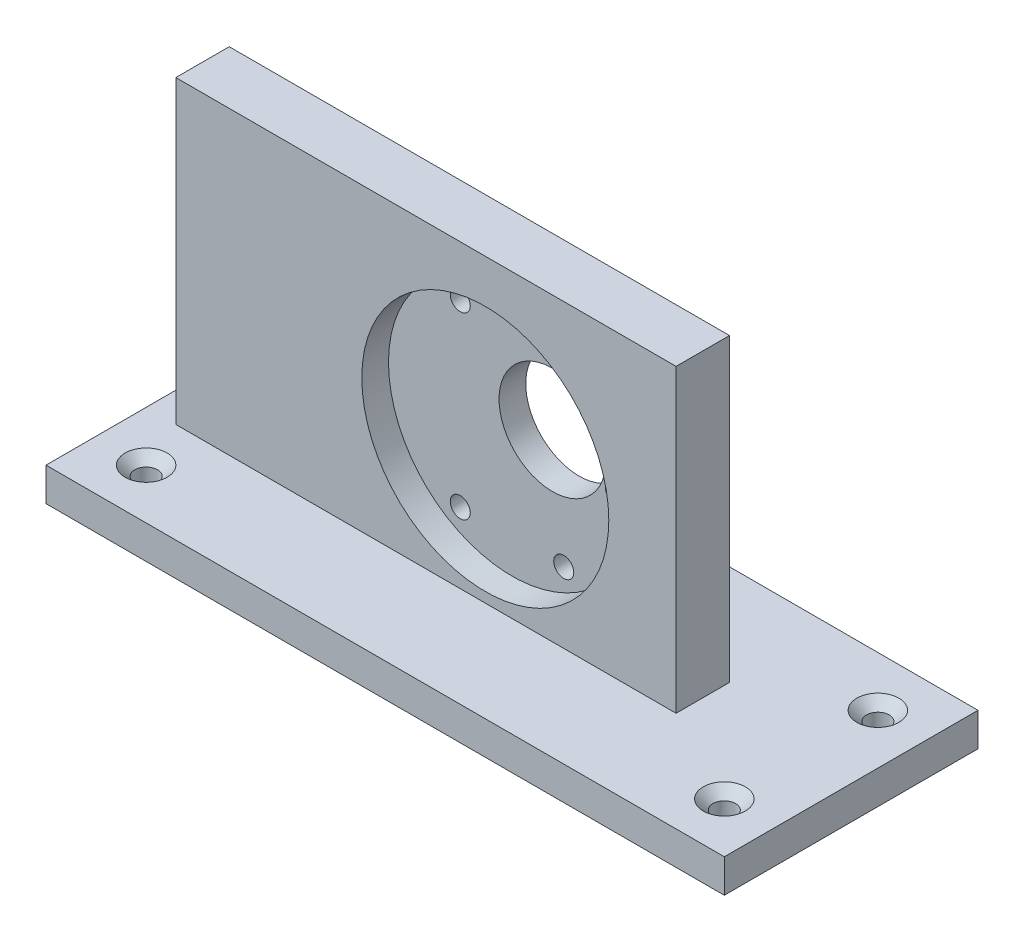
SolidWorks part; units mm, degrees
note: The reader was unsure of these and kept them because the rebuilt part matched: shared geometry of "Sketch3<3>".
other "Markup1"
sketch "Sketch5" plane through (25, 50, 8) normal (0.9645, 0.1424, 0.2224) x (0.1697, 0.3107, -0.9352)
ref_plane "Front Plane" through (0, 0, 0) normal (0, 0, 1) x (1, 0, 0)
ref_plane "Top Plane" through (0, 0, 0) normal (0, 1, 0) x (1, 0, 0)
ref_plane "Right Plane" through (0, 0, 0) normal (1, 0, 0) x (0, 0, -1)
sketch "Sketch3" plane through (0, 0, 0) normal (0, 0, 1) x (1, 0, 0)
  line L1 (-28.575, 50) -> (28.575, 50)
  line L2 (-28.575, 50) -> (-28.575, 0)
  line L3 (-28.575, 0) -> (28.575, 0)
  line L4 (28.575, 50) -> (28.575, 0)
  line L5 (-7.75, 38.4234) -> (7.75, 38.4234) construction
  line L6 (7.75, 38.4234) -> (15.5, 25) construction
  line L7 (15.5, 25) -> (7.75, 11.5766) construction
  line L8 (7.75, 11.5766) -> (-7.75, 11.5766) construction
  line L9 (-7.75, 11.5766) -> (-15.5, 25) construction
  line L10 (-15.5, 25) -> (-7.75, 38.4234) construction
  line L12 (-20.1843, 13.3466) -> (22.8058, 38.167) construction
  circle A5 centre (-7.75, 38.4234) radius 1.5
  circle A6 centre (7.75, 38.4234) radius 1.5
  circle A8 centre (-7.75, 11.5766) radius 1.5
  circle A9 centre (7.75, 11.5766) radius 1.5
  circle A10 centre (15.5, 25) radius 1.5
  circle A11 centre (6.0622, 28.5) radius 8
  point P4 (0, 0)
  point P27 (-11.625, 18.2883)
  point P28 (11.625, 31.7117)
  dimension "D4" = 25
  dimension "D9" = 16
  dimension "D3" = 3
  dimension "D1" = 50
  dimension "D2" = 57.15
  dimension "D6" = 120
  dimension "D7" = 120
  dimension "D8" = 15.5
  dimension "D10" = 6.4234
extrude "Boss-Extrude1" add sketch "Sketch3" along normal blind 8 contours L2 L3 L4 L1
extrude "Cut-Extrude2" cut sketch "Sketch3<3>" along normal blind 10
sketch "Sketch3<3>" plane through (0, 0, 0) normal (0, 0, 1) x (1, 0, 0) same geometry as "Sketch3"
sketch "Sketch4" plane through (0, 0, 8) normal (0, 0, 1) x (1, 0, 0)
  line L0 (-15.5, 25) -> (15.5, 25) construction
  circle A0 centre (0, 25) radius 18.5
  dimension "D1" = 37
extrude "Cut-Extrude3" cut sketch "Sketch4" against normal blind 4 contours A0
sketch "Sketch6" plane through (0, 0, 8) normal (0, 0, 1) x (1, 0, 0)
  line L1 (-50.8, 5) -> (50.8, 5)
  line L2 (-50.8, 5) -> (-50.8, 0)
  line L3 (-50.8, 0) -> (50.8, 0)
  line L4 (50.8, 5) -> (50.8, 0)
  point P4 (0, 0)
  dimension "D1" = 101.6
  dimension "D2" = 5
extrude "Boss-Extrude2" add sketch "Sketch6" against normal blind 23 and the other way blind 15
sketch "Sketch7" plane through (0, 5, 0) normal (0, 1, 0) x (1, 0, 0)
  line L0 (-50.8, -23) -> (-50.8, 15) construction
  line L1 (-50.8, -23) -> (-43.3, -23)
  line L2 (-50.8, -23) -> (-50.8, -15.5)
  line L3 (-50.8, -15.5) -> (-43.3, -15.5)
  line L4 (-43.3, -23) -> (-43.3, -15.5)
  line L5 (-50.8, -4) -> (50.8, -4) construction
  line L6 (50.8, -23) -> (50.8, 15) construction
  line L7 (0, 15) -> (0, -23) construction
  line L8 (50.8, 15) -> (-50.8, 15) construction
  line L9 (50.8, -23) -> (-50.8, -23) construction
  point P18 (-43.3, 7.5)
  point P20 (43.3, -15.5)
  point P21 (43.3, 7.5)
  dimension "D1" = 7.5
hole_wizard "CSK for M3 Flat Head Machine Screw1" positions "Sketch8" profile "Sketch9" countersink size "M3" standard "ANSI Metric" end condition through all
sketch "Sketch8" plane through (0, 5, 0) normal (0, 1, 0) x (1, 0, 0)
  point P0 (-43.3, 7.5)
  point P3 (-43.3, -15.5)
  point P6 (43.3, -15.5)
  point P9 (43.3, 7.5)
sketch "Sketch9" plane through (-43.3, 5, -7.5) normal (1, 0, 0) x (0, 0, 1)
  line L0 (0, 0) -> (0, 5)
  line L1 (0, 5) -> (1.7, 5)
  line L2 (1.7, 5) -> (1.7, 1.45)
  line L3 (1.7, 1.45) -> (3.15, 0)
  line L5 (3.15, 0) -> (0, 0)
  line L6 (-1.7, 1.45) -> (-3.15, 0) construction
  line L11 (0, -6.35) -> (0, 107.95) construction
  dimension "Thru Hole Dia." = 3.4
  dimension "Thru Hole Depth" = 5
  dimension "Near C'Sink Dia." = 6.3
  dimension "Near C'Sink Angle" = 90
extrude "Cut-Extrude6" cut sketch "Sketch16" against normal up to surface (4.826 mm away)
sketch "Sketch16" plane through (-499.2489, 16.8212, -28.3089) normal (0.0361, 0.9993, -0.0009) x (0.0508, -0.0009, 0.9987)
  circle A0 centre (67.5, 464.5) radius 1.7
  circle A2 centre (92.5, 462.5) radius 1.8
  circle A3 centre (113.4, 462.5) radius 1.8
  circle A4 centre (92.5, 401.5) radius 1.8
  circle A5 centre (113.4, 401.5) radius 1.8
  circle A7 centre (67.5, 399.5) radius 1.7
  circle A8 centre (44.5, 399.5) radius 1.7
  circle A9 centre (33.5, 468.8378) radius 1.7
  circle A10 centre (33.5, 435.8378) radius 1.7
  circle A11 centre (44.5, 464.5) radius 1.7
sketch "Sketch17" plane through (0, 5, 0) normal (0, 1, 0) x (1, 0, 0)
  line L1 (-50.8, 15) -> (-25.7177, 15)
  line L2 (-50.8, 15) -> (-50.8, 3.0192)
  line L3 (-50.8, 3.0192) -> (-25.7177, 3.0192)
  line L4 (-25.7177, 15) -> (-25.7177, 3.0192)
extrude "Cut-Extrude7" cut sketch "Sketch17" against normal up to next
sketch "Sketch18" plane through (0, 5, 0) normal (0, 1, 0) x (1, 0, 0)
  line L1 (-28.575, -8) -> (-46.355, -8)
  line L2 (-28.575, -8) -> (-28.575, 0)
  line L3 (-28.575, 0) -> (-46.355, 0)
  line L4 (-46.355, -8) -> (-46.355, 0)
  dimension "D1" = 17.78
  dimension "D2" = 8
extrude "Boss-Extrude3" add sketch "Sketch18" along normal up to vertex (45 mm away)
sketch "Sketch13" plane through (0, 0, 0) normal (0, 0, -1) x (-1, 0, 0)
  line L0 (38.1178, 28.5) -> (-6.0622, 28.5) construction
  circle A5 centre (38.1178, 28.5) radius 4.8006
  circle A7 centre (38.1178, 28.5) radius 6.7056
  dimension "D1" = 9.6012
  dimension "D2" = 1.905
  dimension "D3" = 44.18
extrude "Boss-Extrude4" add sketch "Sketch13" along normal blind 5.08
sketch "Sketch19" plane through (0, 0, 0) normal (0, 0, -1) x (-1, 0, 0)
  circle A0 centre (38.1178, 28.5) radius 4.8006
  dimension "D1" = 9.6012
extrude "Cut-Extrude8" cut sketch "Sketch19" against normal blind 5.08
